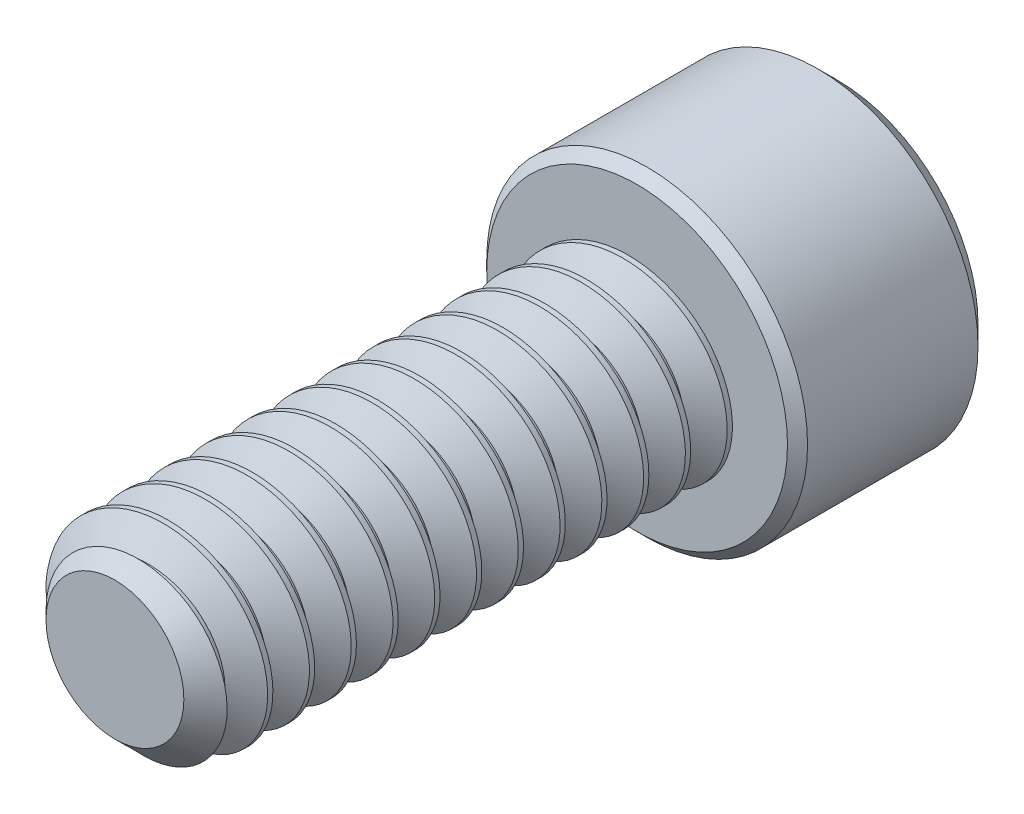
SolidWorks part; units mm, degrees
ref_plane "Front Plane" through (0, 0, 0) normal (0, 0, 1) x (1, 0, 0)
ref_plane "Top Plane" through (0, 0, 0) normal (0, 1, 0) x (1, 0, 0)
ref_plane "Right Plane" through (0, 0, 0) normal (1, 0, 0) x (0, 0, -1)
sketch "Sketch1" plane through (0, 0, 0) normal (0, 0, 1) x (1, 0, 0)
  line L0 (0, 0.762) -> (0, -0.762) construction
  circle A0 centre (0, 0) radius 0.762
  dimension "OD" = 1.524
extrude "Extrude1" add sketch "Sketch1" against normal blind 3.9688
sketch "Sketch2" plane through (0, 0, 0) normal (0, 0, 1) x (1, 0, 0)
  circle A0 centre (0, 0) radius 0.762 construction
  circle A1 centre (0, 0) radius 0.762
curve "Helix/Spiral1" pitch 0.3175 height 4.2862 radius 0.762 centre (0, 0, 0) axis (0, 0, -1) start towards (0, 1, 0) parameters "pitch"=0.3175
chamfer "Chamfer3" distance 0.2381 angle 45 1 edges at (0.762, 0, 0)
sketch "Sketch3" plane through (0, 0, 0) normal (1, 0, 0) x (0, 0, -1)
  line L0 (-0.2778, 0.762) -> (-0.1588, 0.5558)
  line L1 (-0.1588, 0.5558) -> (-0.1191, 0.5558)
  line L2 (-0.1191, 0.5558) -> (0, 0.762)
  line L3 (-0.2778, 0.762) -> (0, 0.762)
  line L4 (-0.1389, 0.762) -> (-0.1389, 0.5558) construction
  line L5 (-0.2183, 0.6589) -> (-0.0595, 0.6589) construction
  line L6 (0, 0.762) -> (0, -0.762) construction
  dimension "D1" = 0.0397
  dimension "D2" = 0.1588
  dimension "D3" = 60
sweep "Cut-Sweep1" cut profiles "Sketch3" path "Helix/Spiral1"
sketch "Sketch6" plane through (0, 0, -3.9688) normal (0, 0, -1) x (-1, 0, 0)
  circle A0 centre (0, 0) radius 1.2192
  dimension "head dia" = 2.4384
extrude "Extrude2" add sketch "Sketch6" along normal blind 1.524
sketch "Sketch7" plane through (0, 0, -5.4928) normal (0, 0, -1) x (-1, 0, 0)
  line L1 (0, 0.7332) -> (-0.635, 0.3666)
  line L2 (-0.635, 0.3666) -> (-0.635, -0.3666)
  line L3 (-0.635, -0.3666) -> (0, -0.7332)
  line L4 (0, -0.7332) -> (0.635, -0.3666)
  line L5 (0.635, -0.3666) -> (0.635, 0.3666)
  line L6 (0.635, 0.3666) -> (0, 0.7332)
  circle A0 centre (0, 0) radius 0.635 construction
  dimension "hex dia" = 1.27
extrude "Cut-Extrude1" cut sketch "Sketch7" against normal blind 0.9525
sketch "Sketch8" plane through (0, 0, -5.4928) normal (0, 0, -1) x (-1, 0, 0)
  circle A0 centre (0, 0) radius 0.7332
extrude "Cut-Extrude2" cut sketch "Sketch8" against normal blind 0.1524 draft 45
chamfer "Chamfer1" distance 0.1524 angle 45 1 edges at (-1.2192, 0, -5.4928)
chamfer "Chamfer2" distance 0.0762 angle 45 1 edges at (-1.2192, 0, -3.9688)
sketch "Sketch9" plane through (0, 0, 0) normal (1, 0, 0) x (0, 0, -1)
  line L0 (0, 0.762) -> (0, -0.762) construction
  line L1 (1.7463, 0.762) -> (1.7463, -0.762) construction
  line L2 (3.9688, 1.2192) -> (3.9688, -1.2192) construction
  line L3 (5.4927, 1.2192) -> (5.4927, -1.2192) construction
  line L4 (5.4928, 0) -> (0, 0) construction
  dimension "D1" = 1.7463
  dimension "D2" = 1.524
  dimension "D3" = 2.4384
  dimension "D4" = 3.9688
equation "\"D3@Helix/Spiral1\" = \"screw length@Extrude1\"+\"pitch@Helix/Spiral1\""
equation "\"D1@Sketch3\" = \"pitch@Helix/Spiral1\"*.125"
equation "\"D2@Sketch3\" = \"pitch@Helix/Spiral1\"*.5"
equation "\"D1@Cut-Extrude1\" = \"hex dia@Sketch7\"*.75"
equation "\"D1@Chamfer1\" = \"head depth@Extrude2\"/10"
equation "\"D1@Sketch9\" = \"pitch@Helix/Spiral1\"*5.5"
equation "\"D1@Chamfer2\" = \"D1@Chamfer1\"/2"
equation "\"D1@Cut-Extrude2\" = \"D1@Chamfer2\"*2"
equation "\"D1@Chamfer3\" = \"pitch@Helix/Spiral1\"*.750"
equation "\"D2@Sketch9\" = \"head depth@Extrude2\""
equation "\"D3@Sketch9\" = \"head dia@Sketch6\""
equation "\"D4@Sketch9\" = \"screw length@Extrude1\""
